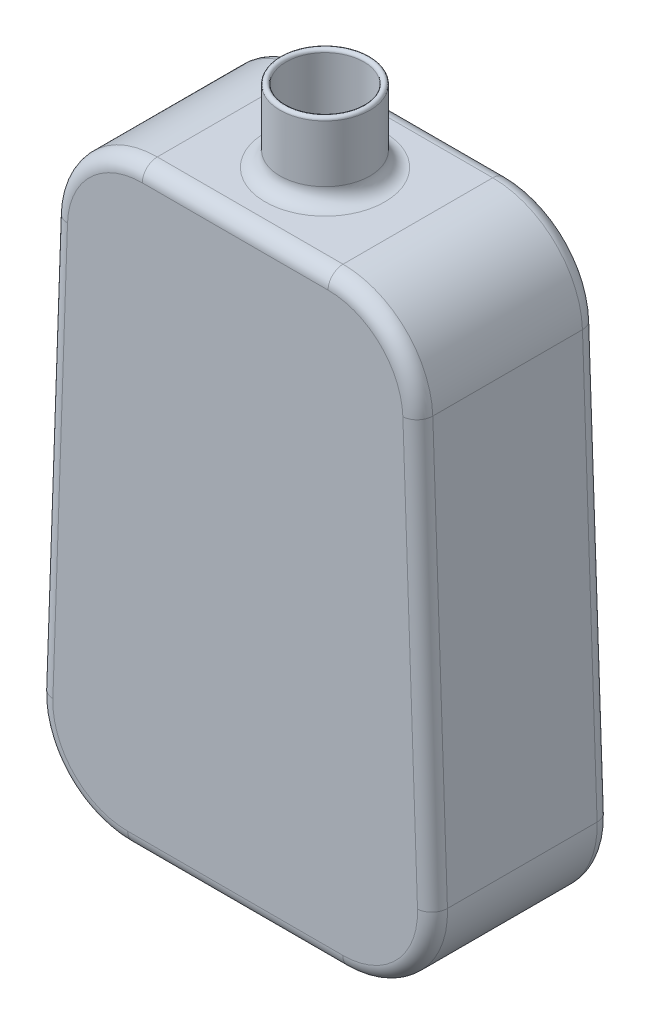
SolidWorks part; units mm, degrees
ref_plane "前视基准面" through (0, 0, 0) normal (0, 0, 1) x (1, 0, 0)
ref_plane "上视基准面" through (0, 0, 0) normal (0, 1, 0) x (1, 0, 0)
ref_plane "右视基准面" through (0, 0, 0) normal (1, 0, 0) x (0, 0, -1)
other "Configuration Table"
sketch "草图1" plane through (0, 0, 0) normal (0, 0, 1) x (1, 0, 0)
  line L0 (0, 47.0291) -> (0, -67.5712) construction
  line L1 (60, 100) -> (-60, 100)
  line L2 (-60, 100) -> (-65.9, -68.953)
  line L3 (-35.9182, -100) -> (35.9182, -100)
  line L4 (60, 100) -> (65.9, -68.953)
  arc A0 (-65.9, -68.953) -> (-35.9182, -100) centre (-35.9182, -70) ccw
  arc A1 (65.9, -68.953) -> (35.9182, -100) centre (35.9182, -70) cw
  point P10 (0, -100)
  point P11 (0, 100)
  dimension "D4" = 30
  dimension "D1" = 2
  dimension "D2" = 60
  dimension "D3" = 200
  dimension "D5" = 100
extrude "凸台-拉伸1" add sketch "草图1" along normal mid plane 60
fillet "圆角1" radius 30 2 edges at (60, 100, 0) (-60, 100, 0)
sketch "草图2" plane through (0, 100, 0) normal (0, 1, 0) x (1, 0, 0)
  circle A0 centre (0, 0) radius 15
  dimension "D1" = 30
extrude "凸台-拉伸2" add sketch "草图2" along normal blind 25
shell "抽壳1" thickness 2 removed face at (-15, 125, 0)
fillet "圆角3" radius 5 17 edges at (51.8691, 91.5802, -30) (63.4555, 1.047, -30) (57.4984, -90.8398, -30) (0, -100, -30) (-57.4984, -90.8398, -30) (-63.4555, 1.047, -30) (-51.8691, 91.5802, -30) (51.8691, 91.5802, 30) (63.4555, 1.047, 30) (57.4984, -90.8398, 30) (0, -100, 30) (-57.4984, -90.8398, 30) (-63.4555, 1.047, 30) (-51.8691, 91.5802, 30) (0, 100, -30) (0, 100, 30) (15, 100, 0)
fillet "圆角4" 2 edges at (-13, 125, 0) (-15, 125, 0) type full round first side face at (-13, 125, 0) second side face at (15, 105, 0) middle face at (-13, 125, 0)
